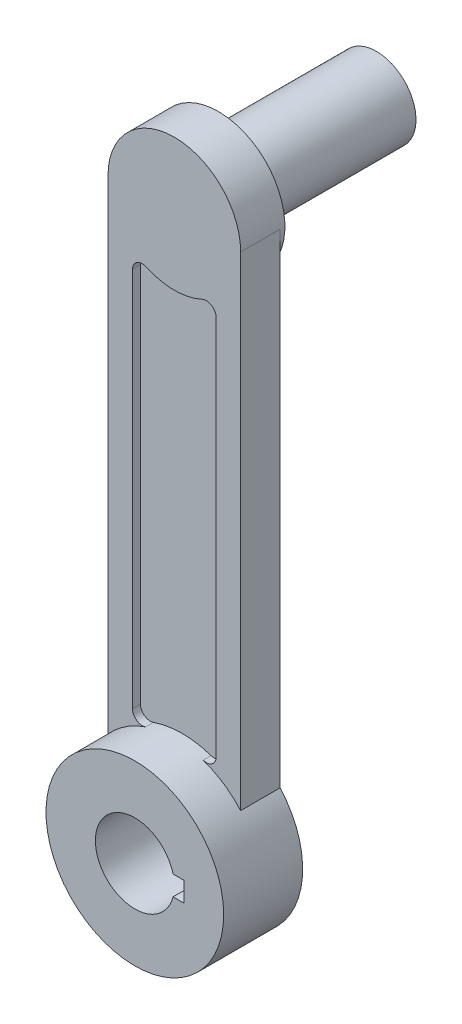
SolidWorks part; units mm, degrees
material "Alloy Steel"
ref_plane "Plane1" through (0, 0, 0) normal (0, 0, 1) x (1, 0, 0)
ref_plane "Plane2" through (0, 0, 0) normal (0, 1, 0) x (1, 0, 0)
ref_plane "Plane3" through (0, 0, 0) normal (1, 0, 0) x (0, 0, -1)
other "Configuration Table"
sketch "Sketch1" plane through (0, 0, 0) normal (0, 0, 1) x (1, 0, 0)
  circle A0 centre (0, 0) radius 28.575
  dimension "D1" = 57.15
extrude "Base pivot" add sketch "Sketch1" along normal mid plane 25.4
sketch "Sketch2" plane through (0, 0, 0) normal (0, 0, 1) x (1, 0, 0)
  line L1 (-21.336, 174.625) -> (-21.336, 0)
  line L2 (21.336, 0) -> (-21.336, 0)
  line L3 (21.336, 0) -> (21.336, 174.625)
  arc A0 (21.336, 174.625) -> (-21.336, 174.625) centre (0, 174.625) ccw
  dimension "D1" = 174.625
  dimension "D2" = 42.672
extrude "Shaft" add sketch "Sketch2" along normal up to surface (12.7 mm away)
sketch "Sketch3" plane through (0, 0, -12.7) normal (0, 0, -1) x (-1, 0, 0)
  circle A0 centre (0, 174.625) radius 21.336
  arc A1 (21.336, 174.625) -> (-21.336, 174.625) centre (0, 174.625) ccw construction
extrude "Top shelf" add sketch "Sketch3" along normal blind 1.524
sketch "Sketch4" plane through (0, 0, -14.224) normal (0, 0, -1) x (-1, 0, 0)
  circle A0 centre (0, 174.625) radius 12.7
  dimension "D1" = 25.4
extrude "Top pin" add sketch "Sketch4" along normal blind 50.8
sketch "Sketch5" plane through (0, 0, 0) normal (0, 0, 1) x (1, 0, 0)
  line L2 (-13.462, 158.0721) -> (-13.462, 25.2053)
  line L3 (13.462, 158.0721) -> (13.462, 25.2053)
  line L4 (0, 0) -> (0, 174.625) construction
  line L5 (21.336, 19.008) -> (21.336, 174.625) construction
  arc A0 (-13.462, 158.0721) -> (13.462, 158.0721) centre (0, 174.625) ccw
  arc A1 (21.336, 19.008) -> (-21.336, 19.008) centre (0, 0) ccw construction
  arc A2 (13.462, 25.2053) -> (-13.462, 25.2053) centre (0, 0) ccw
  arc A3 (21.336, 174.625) -> (-21.336, 174.625) centre (0, 174.625) ccw construction
  dimension "D1" = 7.874
extrude "Front recess" cut sketch "Sketch5" against normal blind 2.54
sketch "Sketch6" plane through (0, 0, -12.7) normal (0, 0, -1) x (-1, 0, 0)
  line L2 (13.462, 158.0721) -> (13.462, 25.2053)
  line L3 (-13.462, 25.2053) -> (-13.462, 158.0721)
  line L4 (13.462, 158.0721) -> (13.462, 25.2053)
  line L5 (-13.462, 25.2053) -> (-13.462, 158.0721)
  arc A2 (-13.462, 158.0721) -> (13.462, 158.0721) centre (0, 174.625) ccw
  arc A3 (13.462, 25.2053) -> (-13.462, 25.2053) centre (0, 0) ccw
  arc A4 (-13.462, 158.0721) -> (13.462, 158.0721) centre (0, 174.625) ccw
  arc A5 (13.462, 25.2053) -> (-13.462, 25.2053) centre (0, 0) ccw
  dimension "D1" = 0
extrude "Back recess" cut sketch "Sketch6" against normal blind 2.54
sketch "Sketch7" plane through (0, 0, 0) normal (0, 0, 1) x (1, 0, 0)
  circle A0 centre (0, 0) radius 12.7
  dimension "D1" = 25.4
extrude "Base hole" cut sketch "Sketch7" against normal through all and the other way through all
sketch "Sketch8" plane through (0, 0, 0) normal (0, 0, 1) x (1, 0, 0)
  line L0 (0, 3.175) -> (15.875, 3.175)
  line L1 (0, 3.175) -> (0, -3.175)
  line L2 (15.875, -3.175) -> (0, -3.175)
  line L3 (15.875, -3.175) -> (15.875, 3.175)
  circle A0 centre (0, 0) radius 12.7 construction
  dimension "D1" = 6.35
  dimension "D2" = 28.575
extrude "Key way" cut sketch "Sketch8" against normal through all and the other way through all
fillet "Fillet1" radius 3.175 8 edges at (-13.462, 158.0721, -1.27) (13.462, 158.0721, -1.27) (13.462, 25.2053, -1.27) (-13.462, 25.2053, -1.27) (13.462, 158.0721, -11.43) (-13.462, 158.0721, -11.43) (-13.462, 25.2053, -11.43) (13.462, 25.2053, -11.43)
sketch "Bearing location" plane through (0, 0, 0) normal (1, 0, 0) x (0, 0, -1)
  line L0 (14.224, 195.961) -> (14.224, 153.289) construction
  line L1 (65.024, 187.325) -> (65.024, 161.925) construction
  line L2 (14.224, 195.961) -> (14.224, 153.289)
  line L3 (65.024, 187.325) -> (65.024, 161.925)
  line L4 (65.024, 174.625) -> (14.224, 174.625)
  point P6 (38.3749, 174.625)
ref_plane "Bearing Center" through (0, 174.625, -38.3749) normal (0, 0, 1) x (1, 0, 0)
